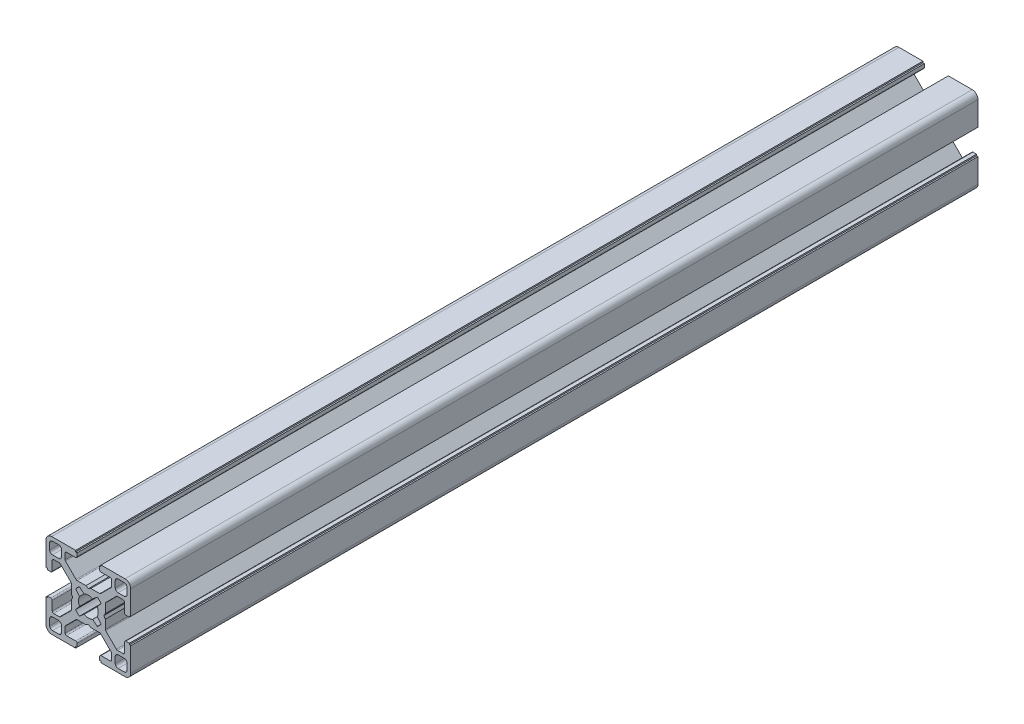
SolidWorks part; units mm, degrees
ref_plane "Front Plane" through (0, 0, 0) normal (0, 0, 1) x (1, 0, 0)
ref_plane "Top Plane" through (0, 0, 0) normal (0, 1, 0) x (1, 0, 0)
ref_plane "Right Plane" through (0, 0, 0) normal (1, 0, 0) x (0, 0, -1)
sketch "Sketch1" plane through (0, 0, 0) normal (0, 0, 1) x (1, 0, 0)
  line L0 (-15, 0) -> (15, 0) construction
  line L1 (0, -15) -> (0, 15) construction
  line L2 (-4.5, 15) -> (4.5, 15) construction
  line L3 (-4, -15) -> (4, -15) construction
  line L4 (-4.5, 15) -> (-4.5, 14.5)
  line L5 (-4.5, 14.5) -> (-4, 14.5)
  line L6 (-4, 14.5) -> (-4, 13.29)
  line L7 (-4.5, 12.79) -> (-7.7675, 12.79)
  line L8 (-8.2675, 12.29) -> (-8.2675, 10.2707)
  line L9 (-8.1211, 9.9171) -> (-4.3504, 6.1464)
  line L10 (-3.9968, 6) -> (0, 6)
  line L11 (0, 0) -> (-15, 15) construction
  line L12 (-4.5, 15) -> (-12.968, 15)
  line L14 (-12.705, 9.5135) -> (-10.5135, 9.5135)
  line L15 (-13.705, 10.5135) -> (-13.705, 12.705)
  line L16 (-12.705, 13.705) -> (-10.5135, 13.705)
  line L17 (-9.5135, 10.5135) -> (-9.5135, 12.705)
  line L18 (-13.705, 9.5135) -> (-9.5135, 13.705) construction
  line L19 (-13.705, 13.705) -> (-9.5135, 9.5135) construction
  line L20 (-3.1568, 4.5038) -> (-1.5303, 3.1477) construction
  line L21 (-4.5038, 3.1568) -> (-3.1477, 1.5303) construction
  line L22 (-6, 3.9968) -> (-6, 0)
  line L23 (-9.9171, 8.1211) -> (-6.1464, 4.3504)
  line L24 (-15, 4.5) -> (-15, 12.968)
  line L25 (-12.29, 8.2675) -> (-10.2707, 8.2675)
  line L26 (-12.79, 4.5) -> (-12.79, 7.7675)
  line L27 (-14.5, 4) -> (-13.29, 4)
  line L28 (-14.5, 4.5) -> (-14.5, 4)
  line L29 (-15, 4.5) -> (-14.5, 4.5)
  circle A0 centre (0, 0) radius 3.5
  arc A1 (-12.968, 15) -> (-15, 12.968) centre (-12.968, 12.968) ccw
  circle A2 centre (0, 0) radius 5.5 construction
  arc A3 (-10.5135, 9.5135) -> (-9.5135, 10.5135) centre (-10.5135, 10.5135) ccw
  arc A4 (-13.705, 12.705) -> (-12.705, 13.705) centre (-12.705, 12.705) cw
  arc A5 (-10.5135, 13.705) -> (-9.5135, 12.705) centre (-10.5135, 12.705) cw
  arc A6 (-12.705, 9.5135) -> (-13.705, 10.5135) centre (-12.705, 10.5135) cw
  arc A7 (-12.79, 4.5) -> (-13.29, 4) centre (-13.29, 4.5) cw
  arc A8 (-12.29, 8.2675) -> (-12.79, 7.7675) centre (-12.29, 7.7675) ccw
  arc A9 (-9.9171, 8.1211) -> (-10.2707, 8.2675) centre (-10.2707, 7.7675) ccw
  arc A10 (-6, 3.9968) -> (-6.1464, 4.3504) centre (-6.5, 3.9968) ccw
  arc A11 (-4.3504, 6.1464) -> (-3.9968, 6) centre (-3.9968, 6.5) ccw
  arc A12 (-4, 13.29) -> (-4.5, 12.79) centre (-4.5, 13.29) cw
  arc A13 (-7.7675, 12.79) -> (-8.2675, 12.29) centre (-7.7675, 12.29) ccw
  arc A14 (-8.2675, 10.2707) -> (-8.1211, 9.9171) centre (-7.7675, 10.2707) ccw
  point P4 (0, 0)
  point P8 (0, 0)
  point P13 (0, 15)
  point P15 (0, -15)
  point P16 (0, 6)
  point P23 (-11.6092, 11.6093)
  point P26 (0, 6)
  point P62 (-12.79, 4)
  point P65 (-12.79, 8.2675)
  point P68 (-10.0636, 8.2675)
  point P71 (-6, 4.2039)
  point P74 (-4.2039, 6)
  point P77 (-4, 12.79)
  point P80 (-8.2675, 12.79)
  point P83 (-8.2675, 10.0636)
  dimension "Center Hole Diameter" = 7
  dimension "D11" = 2.032
  dimension "D9" = 11
  dimension "D13" = 1
  dimension "D14" = 0.5
  dimension "Rail Height" = 30
  dimension "Rail Width" = 30
  dimension "T-Slot Width" = 8
  dimension "T-Slot Depth" = 9
  dimension "D1" = 9
  dimension "D2" = 45
  dimension "D3" = 8
  dimension "D4" = 2.21
  dimension "D5" = 16.535
  dimension "D7" = 2.54
  dimension "D6" = 1.295
  dimension "D8" = 1.246
  dimension "D10" = 10.36
  dimension "D12" = 1.905
sketch "Sketch2" plane through (0, 0, 0) normal (1, 0, 0) x (0, 0, -1)
  line L0 (-76.2, 0) -> (76.2, 0) construction
  line L2 (0, -15) -> (0, 15) construction
  line L3 (0, -15) -> (0, 15) construction
  line L4 (-76.2, -15) -> (-76.2, 15) construction
  line L5 (76.2, -15) -> (76.2, 15) construction
  point P0 (-38.7, 0)
  point P3 (0, 0)
  point P4 (38.7, 0)
  point P12 (-76.2, 0)
  point P14 (76.2, 0)
  dimension "Length" = 152.4
  dimension "D1" = 37.5
sketch "Sketch3" plane through (0, 0, 0) normal (0, 0, 1) x (1, 0, 0)
  line L0 (-4.5038, 3.1568) -> (-3.1477, 1.5303)
  line L1 (0, 3.5) -> (0, 5.5)
  line L2 (-5.5, 0) -> (-3.5, 0)
  line L7 (-6, 3.9968) -> (-6, 0) construction
  line L31 (-9.9171, 8.1211) -> (-6.1464, 4.3504) construction
  line L117 (-12.29, 8.2675) -> (-10.2707, 8.2675) construction
  line L118 (-12.79, 4.5) -> (-12.79, 7.7675) construction
  line L157 (-12.705, 9.5135) -> (-10.5135, 9.5135)
  line L158 (-9.5135, 10.5135) -> (-9.5135, 12.705)
  line L163 (-10.5135, 13.705) -> (-12.705, 13.705)
  line L164 (-13.705, 12.705) -> (-13.705, 10.5135)
  line L165 (-12.705, 9.5135) -> (-10.5135, 9.5135)
  line L166 (-9.5135, 10.5135) -> (-9.5135, 12.705)
  line L167 (-10.5135, 13.705) -> (-12.705, 13.705)
  line L168 (-13.705, 12.705) -> (-13.705, 10.5135)
  line L169 (-14.5, 4) -> (-13.29, 4) construction
  line L170 (-14.5, 4.5) -> (-14.5, 4) construction
  line L171 (-15, 4.5) -> (-14.5, 4.5) construction
  line L172 (-15, 4.5) -> (-15, 12.968) construction
  line L173 (-4.5, 15) -> (-12.968, 15) construction
  line L174 (-4.5, 15) -> (-4.5, 14.5) construction
  line L175 (-4.5, 14.5) -> (-4, 14.5) construction
  line L176 (-4, 14.5) -> (-4, 13.29) construction
  line L177 (-4.5, 12.79) -> (-7.7675, 12.79) construction
  line L178 (-8.2675, 12.29) -> (-8.2675, 10.2707) construction
  line L179 (-8.1211, 9.9171) -> (-4.3504, 6.1464) construction
  line L180 (-3.9968, 6) -> (0, 6) construction
  line L181 (-6, 3.9968) -> (-6, 0.866)
  line L182 (-9.9171, 8.1211) -> (-6.1464, 4.3504)
  line L183 (-12.29, 8.2675) -> (-10.2707, 8.2675)
  line L184 (-12.79, 4.5) -> (-12.79, 7.7675)
  line L185 (-14.5, 4) -> (-13.29, 4)
  line L186 (-14.5, 4.5) -> (-14.5, 4)
  line L187 (-15, 4.5) -> (-14.5, 4.5)
  line L188 (-15, 4.5) -> (-15, 12.968)
  line L189 (-4.5, 15) -> (-12.968, 15)
  line L190 (-4.5, 15) -> (-4.5, 14.5)
  line L191 (-4.5, 14.5) -> (-4, 14.5)
  line L192 (-4, 14.5) -> (-4, 13.29)
  line L193 (-4.5, 12.79) -> (-7.7675, 12.79)
  line L194 (-8.2675, 12.29) -> (-8.2675, 10.2707)
  line L195 (-8.1211, 9.9171) -> (-4.3504, 6.1464)
  line L196 (-3.9968, 6) -> (-0.866, 6)
  line L197 (-0.866, 6) -> (0, 5.5)
  line L198 (0, -15) -> (0, 15) construction
  line L199 (0, 0) -> (-15, 15) construction
  line L200 (0, 0) -> (-15, 15) construction
  line L201 (-3.1568, 4.5038) -> (-1.5303, 3.1477) construction
  line L202 (-3.1568, 4.5038) -> (-1.5303, 3.1477)
  line L203 (-6, 0.866) -> (-5.5, 0)
  line L204 (-15, 0) -> (15, 0) construction
  line L205 (-15, 0) -> (15, 0) construction
  line L206 (0, -15) -> (0, 15) construction
  arc A0 (-3.5, 0) -> (-3.1477, 1.5303) centre (0, 0) cw
  arc A10 (-6, 3.9968) -> (-6.1464, 4.3504) centre (-6.5, 3.9968) ccw construction
  circle A16 centre (0, 0) radius 3.5
  arc A18 (0, 3.5) -> (-1.5303, 3.1477) centre (0, 0) ccw
  arc A20 (-9.9171, 8.1211) -> (-10.2707, 8.2675) centre (-10.2707, 7.7675) ccw construction
  arc A22 (-12.29, 8.2675) -> (-12.79, 7.7675) centre (-12.29, 7.7675) ccw construction
  arc A28 (-13.29, 4) -> (-12.79, 4.5) centre (-13.29, 4.5) ccw construction
  arc A29 (-10.5135, 9.5135) -> (-9.5135, 10.5135) centre (-10.5135, 10.5135) ccw
  arc A30 (-9.5135, 12.705) -> (-10.5135, 13.705) centre (-10.5135, 12.705) ccw
  arc A31 (-12.705, 13.705) -> (-13.705, 12.705) centre (-12.705, 12.705) ccw
  arc A32 (-13.705, 10.5135) -> (-12.705, 9.5135) centre (-12.705, 10.5135) ccw
  arc A33 (-10.5135, 9.5135) -> (-9.5135, 10.5135) centre (-10.5135, 10.5135) ccw
  arc A34 (-9.5135, 12.705) -> (-10.5135, 13.705) centre (-10.5135, 12.705) ccw
  arc A35 (-12.705, 13.705) -> (-13.705, 12.705) centre (-12.705, 12.705) ccw
  arc A36 (-13.705, 10.5135) -> (-12.705, 9.5135) centre (-12.705, 10.5135) ccw
  arc A37 (-12.968, 15) -> (-15, 12.968) centre (-12.968, 12.968) ccw construction
  arc A38 (-4.5, 12.79) -> (-4, 13.29) centre (-4.5, 13.29) ccw construction
  arc A39 (-7.7675, 12.79) -> (-8.2675, 12.29) centre (-7.7675, 12.29) ccw construction
  arc A40 (-8.2675, 10.2707) -> (-8.1211, 9.9171) centre (-7.7675, 10.2707) ccw construction
  arc A41 (-4.3504, 6.1464) -> (-3.9968, 6) centre (-3.9968, 6.5) ccw construction
  arc A42 (-6, 3.9968) -> (-6.1464, 4.3504) centre (-6.5, 3.9968) ccw
  arc A43 (-9.9171, 8.1211) -> (-10.2707, 8.2675) centre (-10.2707, 7.7675) ccw
  arc A44 (-12.29, 8.2675) -> (-12.79, 7.7675) centre (-12.29, 7.7675) ccw
  arc A45 (-13.29, 4) -> (-12.79, 4.5) centre (-13.29, 4.5) ccw
  arc A46 (-12.968, 15) -> (-15, 12.968) centre (-12.968, 12.968) ccw
  arc A47 (-4.5, 12.79) -> (-4, 13.29) centre (-4.5, 13.29) ccw
  arc A48 (-7.7675, 12.79) -> (-8.2675, 12.29) centre (-7.7675, 12.29) ccw
  arc A49 (-8.2675, 10.2707) -> (-8.1211, 9.9171) centre (-7.7675, 10.2707) ccw
  arc A50 (-4.3504, 6.1464) -> (-3.9968, 6) centre (-3.9968, 6.5) ccw
  circle A51 centre (0, 0) radius 5.5 construction
  arc A52 (-3.1568, 4.5038) -> (-4.5038, 3.1568) centre (0, 0) ccw
  dimension "D3" = 60
  dimension "D4" = 60
  dimension "D1" = 0
  dimension "D2" = 0
extrude "Boss-Extrude1" add sketch "Sketch3" along normal mid plane 300
pattern_circular "CirPattern1" count 4 over 360 about axis through (0, 0, 76.2) along (0, 0, -1) of "Boss-Extrude1"
ref_plane "Contact Plane1" through (15, 0, 0) normal (1, 0, 0) x (0, 0, -1)
ref_plane "Contact Plane2" through (0, -15, 0) normal (0, 1, 0) x (1, 0, 0)
ref_plane "Contact Plane3" through (-15, 0, 0) normal (1, 0, 0) x (0, 0, -1)
ref_plane "Contact Plane4" through (0, 15, 0) normal (0, 1, 0) x (1, 0, 0)
equation "\"D1@Sketch2\" = \"Rail Height@Sketch1\" * 1.25"
equation "\"D1@Sketch1\"=\"T-Slot Width@Sketch1\"+1mm"
equation "\"D3@Sketch1\"=\"T-Slot Width@Sketch1\""
equation "\"D1@Boss-Extrude1\"=\"Length\""
equation "\"Length\"= 300mm"
